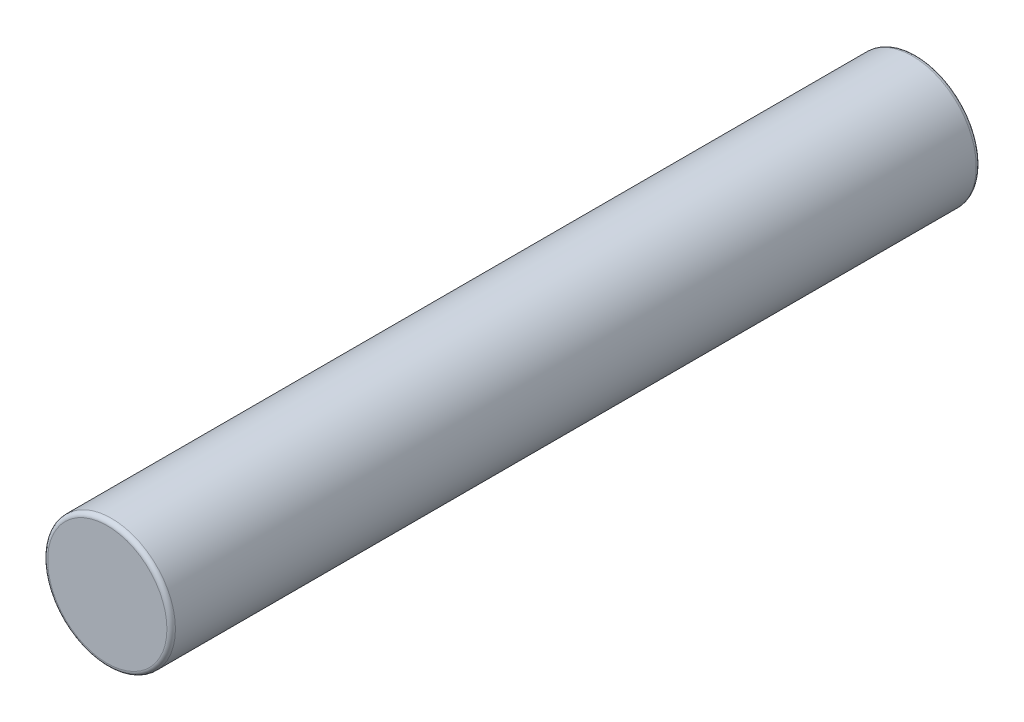
SolidWorks part; units mm, degrees
material "Aleación 1060"
ref_plane "Alzado" through (0, 0, 0) normal (0, 0, 1) x (1, 0, 0)
ref_plane "Planta" through (0, 0, 0) normal (0, 1, 0) x (1, 0, 0)
ref_plane "Vista lateral" through (0, 0, 0) normal (1, 0, 0) x (0, 0, -1)
sketch "Croquis1" plane through (0, 0, 0) normal (0, 0, 1) x (1, 0, 0)
  circle A0 centre (0, 0) radius 0.75
  dimension "D1" = 1.5
extrude "Saliente-Extruir1" add sketch "Croquis1" along normal blind 4.75 and the other way blind 4.75
fillet "Redondeo1" radius 0.05 2 edges at (0.75, 0, -4.75) (0.75, 0, 4.75)
